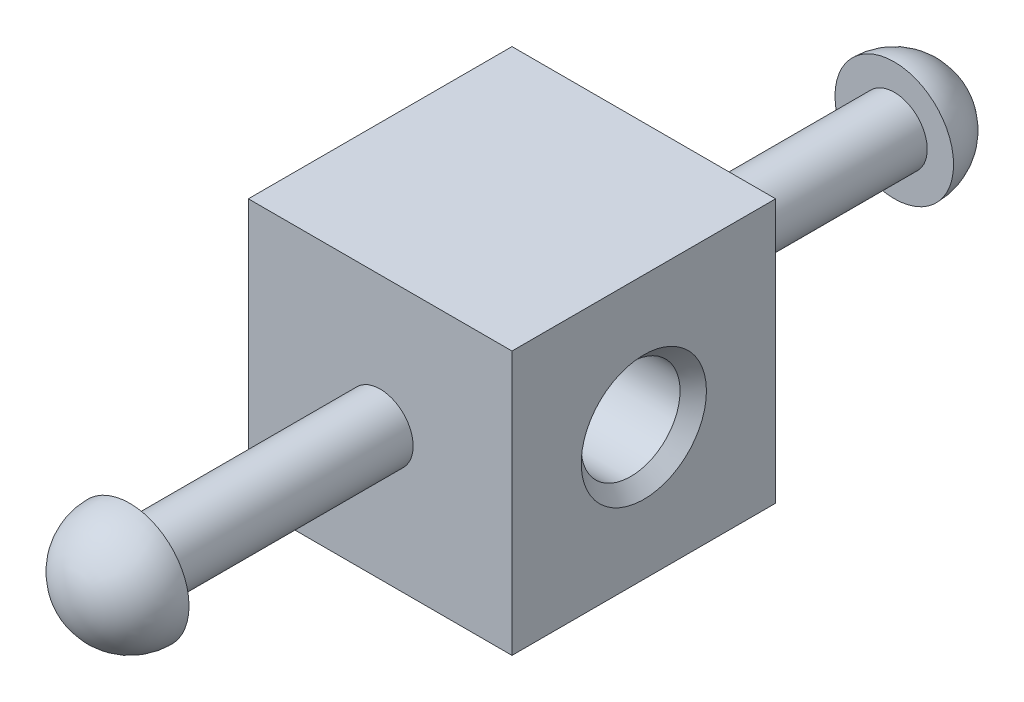
SolidWorks part; units mm, degrees
material "AISI 1020"
ref_plane "Front Plane" through (0, 0, 0) normal (0, 0, 1) x (1, 0, 0)
ref_plane "Top Plane" through (0, 0, 0) normal (0, 1, 0) x (1, 0, 0)
ref_plane "Right Plane" through (0, 0, 0) normal (1, 0, 0) x (0, 0, -1)
sketch "Sketch1" plane through (0, 0, 0) normal (1, 0, 0) x (0, 0, -1)
  line L0 (0, 0) -> (-36.83, 0) construction
  line L1 (12.7, -12.7) -> (-12.7, -12.7)
  line L2 (12.7, -12.7) -> (12.7, 12.7)
  line L3 (12.7, 12.7) -> (-12.7, 12.7)
  line L4 (-12.7, -12.7) -> (-12.7, 12.7)
  line L5 (12.7, -12.7) -> (-12.7, 12.7) construction
  line L6 (12.7, 12.7) -> (-12.7, -12.7) construction
  line L7 (-36.83, 0) -> (-36.83, 3.175)
  line L8 (-36.83, 3.175) -> (-12.7, 3.175)
  line L9 (-36.83, 0) -> (-36.83, -3.175)
  line L10 (-36.83, -3.175) -> (-12.7, -3.175)
  line L11 (0, 12.7) -> (0, -12.7) construction
  line L12 (-36.83, 3.175) -> (-36.83, 5.7123)
  line L13 (24.7135, -6.9171) -> (24.9898, -6.9171) construction
  line L14 (-36.83, -3.175) -> (-36.83, -5.7123)
  line L15 (36.83, 3.175) -> (12.7, 3.175)
  line L16 (36.83, -3.175) -> (12.7, -3.175)
  line L17 (36.83, 0) -> (36.83, -3.175)
  line L18 (36.83, -3.175) -> (36.83, -5.7123)
  line L19 (36.83, 3.175) -> (36.83, 5.7123)
  line L20 (36.83, 0) -> (36.83, 3.175)
  line L21 (-12.7, 0) -> (-42.5423, 0)
  line L22 (12.7, 0) -> (42.5423, 0)
  circle A0 centre (0, 0) radius 4.7625
  arc A1 (-36.83, -5.7123) -> (-36.83, 5.7123) centre (-36.83, 0) cw
  arc A2 (36.83, -5.7123) -> (36.83, 5.7123) centre (36.83, 0) ccw
extrude "Boss-Extrude1" add sketch "Sketch1" along normal mid plane 25.4 contours L4 L1 L2 L3 A0 region at (0, -12.3408, 0)
revolve "Revolve1" add sketch "Sketch1<4>" angle 360 about L21 region at (0, 1.5875, 24.765) region at (0, 2.4244, 39.2544)
sketch "Sketch1<4>" plane through (0, 0, 0) normal (1, 0, 0) x (0, 0, -1) same geometry as "Sketch1"
revolve "Revolve2" add sketch "Sketch1<5>" angle 360 about L22 region at (0, 1.5875, -24.765) region at (0, 2.4244, -39.2544)
sketch "Sketch1<5>" plane through (0, 0, 0) normal (1, 0, 0) x (0, 0, -1) same geometry as "Sketch1"
chamfer "Chamfer1" distance 1.27 angle 45 2 edges at (-12.7, 0, -4.7625) (12.7, 0, -4.7625)
